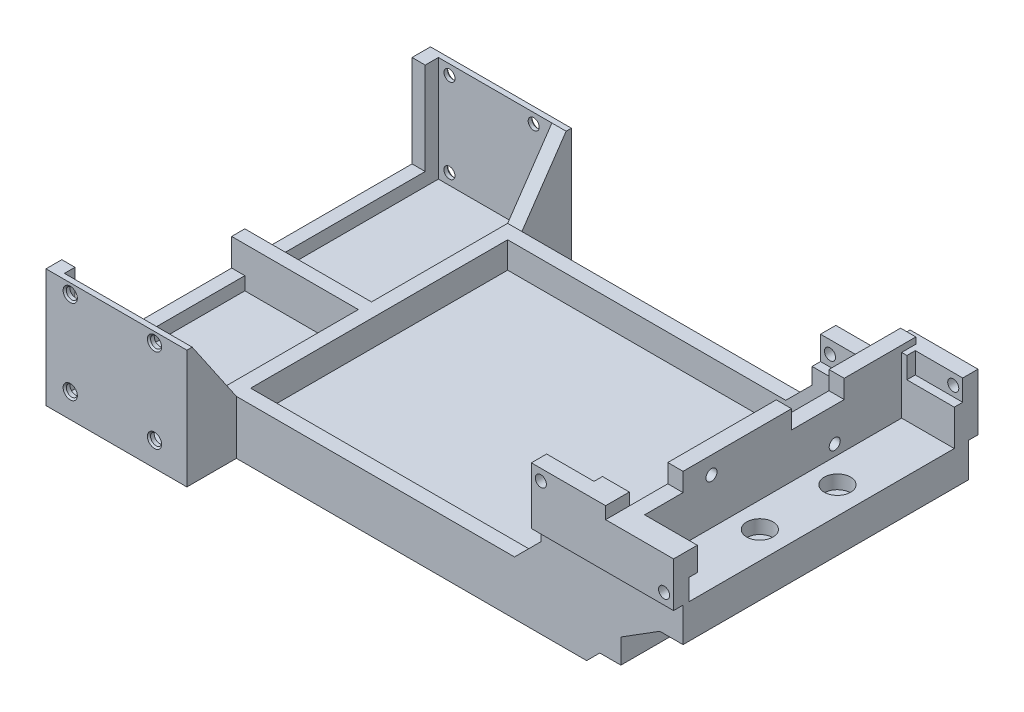
SolidWorks part; units mm, degrees
ref_plane "Front Plane" through (0, 0, 0) normal (0, 0, 1) x (1, 0, 0)
ref_plane "Top Plane" through (0, 0, 0) normal (0, 1, 0) x (1, 0, 0)
ref_plane "Right Plane" through (0, 0, 0) normal (1, 0, 0) x (0, 0, -1)
sketch "Sketch1" plane through (0, 0, 0) normal (0, 1, 0) x (1, 0, 0)
  line L0 (-12.1, 32.5) -> (-12.1, 35.5)
  line L1 (87.8983, -32.4) -> (60.8983, -32.4)
  line L2 (87.8983, -32.4) -> (87.8983, -47)
  line L3 (87.8983, -47) -> (60.8983, -47)
  line L4 (60.8983, -32.4) -> (60.8983, -47)
  line L5 (87.3, 13.5) -> (101.9, 13.5)
  line L6 (87.3, 13.5) -> (87.3, -13.5)
  line L7 (87.3, -13.5) -> (101.9, -13.5)
  line L8 (101.9, 13.5) -> (101.9, -13.5)
  line L9 (60.8983, 32.4) -> (87.8983, 32.4)
  line L10 (60.8983, 32.4) -> (60.8983, 47)
  line L11 (60.8983, 47) -> (87.8983, 47)
  line L12 (87.8983, 32.4) -> (87.8983, 47)
  line L13 (14.3, -24.25) -> (84.3, -24.25)
  line L14 (14.3, -24.25) -> (14.3, 24.25)
  line L15 (14.3, 24.25) -> (84.3, 24.25)
  line L16 (84.3, -24.25) -> (84.3, 24.25)
  line L17 (-12.1, 2.5) -> (10.1, 2.5)
  line L18 (-12.1, 2.5) -> (-12.1, 10.5)
  line L19 (-12.1, 35.5) -> (10.1, 35.5)
  line L20 (10.1, 2.5) -> (10.1, 10.5)
  line L21 (10.1, -35.5) -> (-10.1, -35.5)
  line L22 (10.1, -35.5) -> (10.1, -32.5)
  line L23 (10.1, -2.5) -> (-10.1, -2.5)
  line L24 (-10.1, -35.5) -> (-10.1, -32.5)
  line L25 (-16.1, -32.5) -> (-10.1, -32.5)
  line L26 (-16.1, -32.5) -> (-16.1, -10.5)
  line L27 (-16.1, -10.5) -> (-10.1, -10.5)
  line L28 (11.3, -32.5) -> (11.3, -10.5)
  line L29 (-16.1, 10.5) -> (-12.1, 10.5)
  line L30 (-16.1, 10.5) -> (-16.1, 32.5)
  line L31 (-16.1, 32.5) -> (-12.1, 32.5)
  line L32 (11.3, 10.5) -> (11.3, 32.5)
  line L33 (10.1, 10.5) -> (11.3, 10.5)
  line L34 (10.1, 32.5) -> (10.1, 35.5)
  line L35 (10.1, 32.5) -> (11.3, 32.5)
  line L36 (10.1, -10.5) -> (11.3, -10.5)
  line L37 (10.1, -10.5) -> (10.1, -2.5)
  line L38 (-10.1, -10.5) -> (-10.1, -2.5)
  line L39 (10.1, -32.5) -> (11.3, -32.5)
  arc A0 (90.0992, 6.7139) -> (90.0992, -6.7139) centre (93.8, 0) ccw
  arc A1 (91.0805, -8.0067) -> (96.5195, -8.0067) centre (93.8, -7.366) ccw
  arc A2 (96.5195, 8.0067) -> (91.0805, 8.0067) centre (93.8, 7.366) ccw
  arc A3 (97.5008, -6.7139) -> (97.5008, 6.7139) centre (93.8, 0) ccw
  arc A4 (96.5195, -8.0067) -> (97.5008, -6.7139) centre (98.4662, -8.4654) cw
  arc A5 (90.0992, 6.7139) -> (91.0805, 8.0067) centre (89.1338, 8.4654) ccw
  arc A6 (91.0805, -8.0067) -> (90.0992, -6.7139) centre (89.1338, -8.4654) ccw
  arc A7 (97.5008, 6.7139) -> (96.5195, 8.0067) centre (98.4662, 8.4654) cw
  point P33 (96.585, -7.1425)
  dimension "D1" = 2
  dimension "D2" = 2
  dimension "D3" = 2
  dimension "D36" = 7.6663
  dimension "D37" = 7.366
  dimension "D39" = 2.794
  dimension "D4" = 22.2
  dimension "D5" = 3
  dimension "D6" = 22
  dimension "D7" = 4
  dimension "D8" = 1.2
  dimension "D9" = 3
  dimension "D10" = 70
  dimension "D11" = 48.5
  dimension "D12" = 20.2
  dimension "D13" = 6
  dimension "D14" = 1.2
  dimension "D15" = 3
  dimension "D16" = 22
  dimension "D17" = 8
  dimension "D18" = 3
  dimension "D19" = 11.5
  dimension "D20" = 11.5
  dimension "D21" = 27
  dimension "D22" = 14.6
  dimension "D23" = 27
  dimension "D24" = 14.6
  dimension "D25" = 49.5983
  dimension "D26" = 49.5983
  dimension "D27" = 8
  dimension "D28" = 5
  dimension "D29" = 8.15
  dimension "D30" = 3
  dimension "D31" = 10.75
  dimension "D32" = 9.5
  dimension "D33" = 24.25
  dimension "D34" = 27
  dimension "D35" = 14.6
  dimension "D38" = 7.366
  dimension "D40" = 14.3
  dimension "D41" = 2.5
sketch "Sketch5" plane through (0, 0, 0) normal (0, 1, 0) x (1, 0, 0)
  line L0 (87.15, 27.1) -> (11.45, 27.1)
  line L1 (84.3, 24.25) -> (14.3, 24.25) construction
  line L2 (84.3, 24.25) -> (84.3, -24.25) construction
  line L3 (84.3, -24.25) -> (14.3, -24.25) construction
  line L4 (14.3, 24.25) -> (14.3, -24.25) construction
  line L5 (11.45, 27.1) -> (11.45, -27.1)
  line L6 (87.15, -27.1) -> (11.45, -27.1)
  line L7 (87.15, 27.1) -> (87.15, 3.8718)
  line L8 (87.15, -3.8718) -> (87.15, -27.1)
  line L9 (14.15, 24.4) -> (14.15, -24.4)
  line L10 (87.15, 27.1) -> (87.15, -27.1) construction
  line L11 (84.45, -24.4) -> (14.15, -24.4)
  line L12 (84.45, 24.4) -> (84.45, -24.4)
  line L13 (84.45, 24.4) -> (14.15, 24.4)
  arc A0 (87.15, 3.8718) -> (87.15, -3.8718) centre (93.8, 0) ccw
  dimension "D2" = 15.39
  dimension "D1" = 2.85
  dimension "D3" = 0.15
extrude "Boss-Extrude2" add sketch "Sketch5" along normal blind 5
sketch "Sketch6" plane through (0, 0, 0) normal (0, -1, 0) x (1, 0, 0)
  line L0 (87.15, -3.8718) -> (87.15, -27.1)
  line L1 (11.45, 27.1) -> (87.15, 27.1)
  line L2 (11.45, 27.1) -> (11.45, -27.1)
  line L3 (11.45, -27.1) -> (87.15, -27.1)
  line L4 (87.15, 27.1) -> (87.15, 3.8718)
  arc A0 (87.15, 3.8718) -> (87.15, -3.8718) centre (93.8, 0) ccw
  dimension "D1" = 15.39
extrude "Boss-Extrude4" add sketch "Sketch6" along normal blind 2.7
sketch "Sketch7" plane through (0, 5, 0) normal (0, 1, 0) x (1, 0, 0)
  line L1 (87.15, -27.1) -> (79.15, -27.1)
  line L2 (11.45, -27.1) -> (87.15, -27.1) construction
  line L3 (79.15, -27.1) -> (79.15, -24.4)
  line L4 (14.15, -24.4) -> (84.45, -24.4) construction
  line L5 (79.15, -24.4) -> (84.45, -24.4)
  line L6 (84.45, -24.4) -> (84.45, 24.4)
  line L7 (84.45, 24.4) -> (79.15, 24.4)
  line L8 (84.45, 24.4) -> (14.15, 24.4) construction
  line L9 (79.15, 24.4) -> (79.15, 27.1)
  line L10 (87.15, 27.1) -> (11.45, 27.1) construction
  line L11 (79.15, 27.1) -> (87.15, 27.1)
  line L14 (87.15, 27.1) -> (87.15, 3.8718)
  line L15 (87.15, -3.8718) -> (87.15, -27.1)
  arc A0 (87.15, 3.8718) -> (87.15, -3.8718) centre (93.8, 0) ccw
  dimension "D1" = 15.39
  dimension "D2" = 8
  dimension "D3" = 8
extrude "Boss-Extrude5" add sketch "Sketch7" along normal blind 1.575
sketch "Sketch8" plane through (0, 6.575, 0) normal (0, 1, 0) x (1, 0, 0)
  line L0 (79.15, -27.1) -> (87.15, -27.1) construction
  line L1 (84.45, -27.1) -> (101.95, -27.1)
  line L2 (84.45, -27.1) -> (84.45, 27.1)
  line L3 (84.45, 27.1) -> (101.95, 27.1)
  line L4 (101.95, -27.1) -> (101.95, 27.1)
  line L5 (84.45, -27.1) -> (87.15, -27.1) construction
  dimension "D1" = 54.2
  dimension "D2" = 17.5
  dimension "D3" = 2.7
extrude "Boss-Extrude6" add sketch "Sketch8" along normal blind 6.5
sketch "Sketch9" plane through (0, 0, 27.1) normal (0, 0, 1) x (1, 0, 0)
  line L0 (84.45, 13.075) -> (79.15, 6.575)
  line L1 (79.15, 6.575) -> (84.45, 6.575)
  line L2 (84.45, 6.575) -> (84.45, 13.075)
extrude "Boss-Extrude7" add sketch "Sketch9" against normal through all
sketch "Sketch10" plane through (0, 0, 0) normal (0, 1, 0) x (1, 0, 0)
  line L0 (84.45, 27.1) -> (84.45, -27.1) construction
  line L1 (14.15, 24.4) -> (84.45, 24.4)
  line L2 (14.15, 24.4) -> (14.15, -24.4)
  line L3 (14.15, -24.4) -> (84.45, -24.4)
  line L4 (84.45, 24.4) -> (84.45, -24.4)
  line L5 (14.15, -24.4) -> (84.45, -24.4) construction
extrude "Cut-Extrude1" cut sketch "Sketch10" along normal through all
sketch "Sketch11" plane through (0, 0, 27.1) normal (0, 0, 1) x (1, 0, 0)
  line L0 (94.55, 6.575) -> (87.15, 1.9375)
  line L1 (87.15, 6.575) -> (101.95, 6.575) construction
  line L2 (87.15, 6.575) -> (87.15, -2.7) construction
  line L3 (87.15, 1.9375) -> (87.15, 6.575)
  line L4 (87.15, 6.575) -> (94.55, 6.575)
extrude "Boss-Extrude8" add sketch "Sketch11" against normal blind 5
sketch "Sketch12" plane through (0, 0, -27.1) normal (0, 0, -1) x (-1, 0, 0)
  line L0 (-94.55, 6.575) -> (-87.15, 1.9375)
  line L1 (-101.95, 6.575) -> (-87.15, 6.575) construction
  line L2 (-87.15, 6.575) -> (-87.15, -2.7) construction
  line L3 (-87.15, 1.9375) -> (-87.15, 6.575)
  line L4 (-87.15, 6.575) -> (-94.55, 6.575)
extrude "Boss-Extrude9" add sketch "Sketch12" against normal blind 5
sketch "Sketch13" plane through (0, 13.075, 0) normal (0, 1, 0) x (1, 0, 0)
  line L1 (84.45, 27.1) -> (88.95, 27.1)
  line L2 (84.45, 27.1) -> (84.45, -27.1)
  line L3 (84.45, -27.1) -> (88.95, -27.1)
  line L4 (88.95, 27.1) -> (88.95, -27.1)
  dimension "D1" = 4.5
extrude "Boss-Extrude10" add sketch "Sketch13" along normal blind 12
sketch "Sketch15" plane through (0, 13.075, 0) normal (0, 1, 0) x (1, 0, 0)
  circle A0 centre (93.8, 7.366) radius 1
  circle A1 centre (93.8, -7.366) radius 1
  dimension "D1" = 2
  dimension "D2" = 2
extrude "Cut-Extrude3" cut sketch "Sketch15" against normal through all
sketch "Sketch16" plane through (0, 13.075, 0) normal (0, 1, 0) x (1, 0, 0)
  circle A0 centre (93.8, 7.366) radius 2.5
  circle A1 centre (93.8, -7.366) radius 2.5
  dimension "D1" = 5
extrude "Cut-Extrude4" cut sketch "Sketch16" against normal offset from surface (2.6 mm away) 3.9 up to face at (93.8, 6.575, -8.366)
sketch "Sketch17" plane through (0, 13.075, 0) normal (0, 1, 0) x (1, 0, 0)
  line L0 (88.95, -27.1) -> (101.95, -27.1) construction
  line L1 (101.95, 27.1) -> (98.95, 27.1)
  line L2 (101.95, 27.1) -> (101.95, -27.1)
  line L3 (101.95, -27.1) -> (98.95, -27.1)
  line L4 (98.95, 27.1) -> (98.95, -27.1)
  dimension "D1" = 3
extrude "Cut-Extrude5" cut sketch "Sketch17" against normal through all
sketch "Sketch18" plane through (84.45, 0, 0) normal (-1, 0, 0) x (0, 0, 1)
  line L0 (0, 25.075) -> (-13.5, 25.075) construction
  line L1 (-27.1, 25.075) -> (27.1, 25.075) construction
  line L3 (-13.5, 25.075) -> (-3.5, 25.075)
  line L4 (-13.5, 25.075) -> (-13.5, 21.575)
  line L5 (-13.5, 21.575) -> (-3.5, 21.575)
  line L6 (-3.5, 25.075) -> (-3.5, 21.575)
  dimension "D1" = 13.5
  dimension "D2" = 8.5
  dimension "D3" = 10
extrude "Cut-Extrude6" cut sketch "Sketch18" against normal through all
sketch "Sketch19" plane through (88.95, 0, 0) normal (1, 0, 0) x (0, 0, -1)
  line L0 (-27.1, 25.075) -> (27.1, 25.075) construction
  line L1 (0, 13.075) -> (0, 23.875) construction
  line L3 (-11.7, 18.475) -> (11.7, 18.475) construction
  line L4 (11.7, 18.475) -> (11.7, 15.175) construction
  line L5 (-11.7, 18.475) -> (-11.7, 21.775) construction
  line L6 (27.1, 13.075) -> (-27.1, 13.075) construction
  circle A0 centre (-11.7, 21.775) radius 1.05
  circle A1 centre (11.7, 15.175) radius 1.05
  point P11 (0, 18.475)
  point P15 (0, 18.475)
  dimension "D3" = 2.1
  dimension "D4" = 2.1
  dimension "D1" = 23.4
  dimension "D2" = 2.1
  dimension "D5" = 10.8
extrude "Cut-Extrude7" cut sketch "Sketch19" against normal through all
sketch "Sketch20" plane through (0, 25.075, 0) normal (0, 1, 0) x (1, 0, 0)
  line L0 (88.95, 27.1) -> (84.45, 27.1) construction
  line L1 (84.45, -27.1) -> (86.05, -27.1)
  line L2 (84.45, -27.1) -> (84.45, 27.1)
  line L3 (84.45, 27.1) -> (86.05, 27.1)
  line L4 (86.05, -27.1) -> (86.05, 27.1)
  dimension "D1" = 1.6
extrude "Cut-Extrude8" cut sketch "Sketch20" against normal up to vertex (12 mm away) up to point (84.45, 13.075, -24.4)
sketch "Sketch21" plane through (0, 0, 27.1) normal (0, 0, 1) x (1, 0, 0)
  line L0 (98.95, 13.075) -> (98.95, 15.175) construction
  line L1 (88.95, 13.075) -> (98.95, 13.075)
  line L2 (88.95, 13.075) -> (88.95, 18.075)
  line L3 (88.95, 18.075) -> (98.95, 18.075)
  line L4 (98.95, 13.075) -> (98.95, 18.075)
  line L5 (98.95, 15.175) -> (97.15, 15.175) construction
  line L6 (98.95, 6.575) -> (98.95, 13.075) construction
  circle A0 centre (97.15, 15.175) radius 1.05
  point P8 (98.9208, 15.175)
  dimension "D4" = 2.1
  dimension "D1" = 5
  dimension "D2" = 2.1
  dimension "D3" = 1.8
extrude "Boss-Extrude11" add sketch "Sketch21" against normal blind 2.7 and the other way blind 1.8
sketch "Sketch23" plane through (0, 0, 27.1) normal (0, 0, 1) x (1, 0, 0)
  line L0 (71.95, 23.875) -> (71.95, 21.775) construction
  line L1 (98.95, 13.075) -> (71.95, 13.075)
  line L2 (98.95, 13.075) -> (98.95, 23.875)
  line L3 (98.95, 23.875) -> (71.95, 23.875)
  line L4 (71.95, 13.075) -> (71.95, 23.875)
  line L5 (71.95, 21.775) -> (73.75, 21.775) construction
  circle A0 centre (73.75, 21.775) radius 1.05
  circle A1 centre (97.15, 15.175) radius 1.05
  dimension "D5" = 2.1
  dimension "D6" = 2.1
  dimension "D1" = 10.8
  dimension "D2" = 27
  dimension "D3" = 2.1
  dimension "D4" = 1.8
extrude "Boss-Extrude13" add sketch "Sketch23" along normal blind 1.8 and the other way blind 2.7
sketch "Sketch22" plane through (86.05, 0, 0) normal (-1, 0, 0) x (0, 0, 1)
  line L0 (27.1, 25.075) -> (33.6651, 25.075)
  line L1 (27.1, 25.075) -> (17.1, 25.075)
  line L3 (27.1, 21.575) -> (17.1, 21.575)
  line L4 (17.1, 25.075) -> (17.1, 21.575)
  line L5 (33.6651, 25.075) -> (33.6651, 21.575)
  line L6 (33.6651, 21.575) -> (27.1, 21.575)
  dimension "D2" = 10
  dimension "D3" = 3.5
extrude "Cut-Extrude9" cut sketch "Sketch22" against normal through all
sketch "Sketch24" plane through (0, 0, 27.1) normal (0, 0, 1) x (1, 0, 0)
  line L1 (71.95, 13.075) -> (85.45, 13.075)
  line L2 (71.95, 13.075) -> (71.95, 5)
  line L3 (71.95, 5) -> (85.45, 5)
  line L4 (85.45, 13.075) -> (85.45, 5)
extrude "Boss-Extrude14" add sketch "Sketch24" against normal up to surface (2.7 mm away) up to face at (59.25, 4.9417, 24.4)
sketch "Sketch25" plane through (0, 0, -27.1) normal (0, 0, -1) x (-1, 0, 0)
  line L0 (-98.95, 23.875) -> (-98.95, 21.775) construction
  line L1 (-98.95, 13.075) -> (-71.95, 13.075)
  line L2 (-98.95, 13.075) -> (-98.95, 23.875)
  line L3 (-98.95, 23.875) -> (-86.05, 23.875)
  line L5 (-98.95, 21.775) -> (-97.15, 21.775) construction
  line L6 (-71.95, 13.075) -> (-71.95, 15.175) construction
  line L7 (-71.95, 15.175) -> (-73.75, 15.175) construction
  line L9 (-71.95, 17.575) -> (-80.95, 17.575)
  line L10 (-80.95, 17.575) -> (-86.05, 23.875)
  line L11 (-71.95, 17.575) -> (-71.95, 13.075)
  circle A0 centre (-97.15, 21.775) radius 1.05
  circle A1 centre (-73.75, 15.175) radius 1.05
  point P1 (-73.2063, 14.7578)
  dimension "D3" = 2.1
  dimension "D1" = 2.1
  dimension "D2" = 1.8
  dimension "D4" = 2.1
  dimension "D5" = 1.8
  dimension "D6" = 4.5
  dimension "D7" = 9
  dimension "D8" = 27
extrude "Boss-Extrude15" add sketch "Sketch25" along normal blind 1.8 and the other way blind 2.7
sketch "Sketch26" plane through (0, 0, -24.4) normal (0, 0, 1) x (1, 0, 0)
  line L0 (84.45, 13.075) -> (71.95, 13.075) construction
  line L1 (71.95, 17.575) -> (80.95, 17.575)
  line L2 (71.95, 17.575) -> (71.95, 13.075)
  line L3 (71.95, 13.075) -> (80.95, 13.075)
  line L4 (80.95, 17.575) -> (80.95, 13.075)
extrude "Cut-Extrude10" cut sketch "Sketch26" against normal blind 1.6
sketch "Sketch27" plane through (0, 0, 24.4) normal (0, 0, -1) x (-1, 0, 0)
  line L1 (-71.95, 23.875) -> (-80.95, 23.875)
  line L2 (-71.95, 23.875) -> (-71.95, 19.875)
  line L3 (-71.95, 19.875) -> (-80.95, 19.875)
  line L4 (-80.95, 23.875) -> (-80.95, 19.875)
  dimension "D1" = 4
  dimension "D2" = 9
extrude "Cut-Extrude11" cut sketch "Sketch27" against normal blind 1.6
sketch "Sketch28" plane through (0, 0, -24.4) normal (0, 0, 1) x (1, 0, 0)
  line L1 (98.95, 23.875) -> (89.95, 23.875)
  line L2 (98.95, 23.875) -> (98.95, 19.875)
  line L3 (98.95, 19.875) -> (89.95, 19.875)
  line L4 (89.95, 23.875) -> (89.95, 19.875)
  dimension "D1" = 4
  dimension "D2" = 9
extrude "Cut-Extrude12" cut sketch "Sketch28" against normal blind 1.6
sketch "Sketch29" plane through (0, 0, 24.4) normal (0, 0, -1) x (-1, 0, 0)
  line L1 (-98.95, 13.075) -> (-89.95, 13.075)
  line L2 (-98.95, 13.075) -> (-98.95, 17.075)
  line L3 (-98.95, 17.075) -> (-89.95, 17.075)
  line L4 (-89.95, 13.075) -> (-89.95, 17.075)
  dimension "D1" = 4
  dimension "D2" = 9
extrude "Cut-Extrude13" cut sketch "Sketch29" against normal blind 1.6
sketch "Sketch30" plane through (0, 0, -27.1) normal (0, 0, -1) x (-1, 0, 0)
  line L1 (-71.95, 13.075) -> (-86.6707, 13.075)
  line L2 (-71.95, 13.075) -> (-71.95, 5)
  line L3 (-71.95, 5) -> (-86.6707, 5)
  line L4 (-86.6707, 13.075) -> (-86.6707, 5)
extrude "Boss-Extrude16" add sketch "Sketch30" against normal blind 2.7
sketch "Sketch31" plane through (0, -2.7, 0) normal (0, -1, 0) x (1, 0, 0)
  line L0 (87.15, 27.1) -> (80.65, 27.1) construction
  line L1 (87.15, 27.1) -> (11.45, 27.1) construction
  line L3 (80.65, 27.1) -> (-12.6, 27.1)
  line L4 (80.65, 27.1) -> (80.65, -27.1)
  line L5 (80.65, -27.1) -> (-12.6, -27.1)
  line L6 (-12.6, 27.1) -> (-12.6, -27.1)
  dimension "D1" = 6.5
  dimension "D2" = 24.05
extrude "Boss-Extrude17" add sketch "Sketch31" along normal blind 2.5
sketch "Sketch33" plane through (0, -5.2, 0) normal (0, -1, 0) x (1, 0, 0)
  line L0 (-12.6, 0) -> (0, 0) construction
  line L1 (-12.6, 27.1) -> (-12.6, -27.1) construction
  line L2 (-12.6, -1.25) -> (11.45, -1.25)
  line L3 (-12.6, 1.25) -> (11.45, 1.25)
  line L4 (0, 0) -> (11.45, 0) construction
  line L5 (11.45, 27.1) -> (11.45, -27.1) construction
  line L6 (-12.6, -1.25) -> (0, -1.25) construction
  line L7 (-12.6, 1.25) -> (0, 1.25) construction
  line L8 (-12.6, 1.25) -> (-12.6, -1.25)
  line L9 (11.45, 1.25) -> (11.45, -1.25)
  dimension "D1" = 1.25
  dimension "D2" = 1.25
extrude "Boss-Extrude18" add sketch "Sketch33" against normal up to surface (10.2 mm away) up to face at (42.375, 5, 0)
sketch "Sketch36" plane through (0, -5.2, 0) normal (0, -1, 0) x (1, 0, 0)
  line L1 (-12.6, 27.1) -> (11.45, 27.1)
  line L2 (-12.6, 27.1) -> (-12.6, 36.5)
  line L3 (-12.6, 36.5) -> (11.45, 36.5)
  line L4 (11.45, 27.1) -> (11.45, 36.5)
  point P5 (0, 0)
  point P7 (0, 0)
  point P8 (0, 0)
  point P9 (0, 0)
  dimension "D1" = 9.4
extrude "Boss-Extrude20" add sketch "Sketch36" against normal up to surface (2.5 mm away) up to face at (-0.575, -2.7, 14.175)
sketch "Sketch37" plane through (0, -2.7, 0) normal (0, 1, 0) x (1, 0, 0)
  line L0 (11.45, -27.1) -> (11.45, -36.5) construction
  line L1 (-12.6, -36.5) -> (11.45, -36.5)
  line L2 (-12.6, -36.5) -> (-12.6, -35.5)
  line L3 (-12.6, -35.5) -> (11.45, -35.5)
  line L4 (11.45, -36.5) -> (11.45, -35.5)
  dimension "D1" = 1
extrude "Boss-Extrude21" add sketch "Sketch37" along normal blind 20
sketch "Sketch38" plane through (0, 0, 36.5) normal (0, 0, 1) x (1, 0, 0)
  line L0 (0, 17.3) -> (8, 17.3) construction
  line L1 (-12.6, 17.3) -> (11.45, 17.3) construction
  line L2 (8, 17.3) -> (8, 15.4) construction
  line L3 (8, 15.4) -> (-8, 15.4) construction
  line L4 (8, 15.4) -> (8, -0.6) construction
  line L5 (-8, 15.4) -> (-8, -0.6) construction
  circle A0 centre (8, 15.4) radius 1.05
  circle A1 centre (8, -0.6) radius 1.05
  circle A2 centre (-8, 15.4) radius 1.05
  circle A3 centre (-8, -0.6) radius 1.05
  point P12 (0, 0)
  point P14 (-8.0018, 15.3)
  dimension "D3" = 2.1
  dimension "D1" = 8
  dimension "D2" = 1.9
  dimension "D4" = 16
  dimension "D5" = 16
  dimension "D6" = 16
extrude "Cut-Extrude14" cut sketch "Sketch38" against normal up to next
sketch "Sketch39" plane through (0, -2.7, 0) normal (0, 1, 0) x (1, 0, 0)
  line L0 (11.45, -27.1) -> (71.95, -27.1) construction
  line L1 (11.45, -36.5) -> (14.15, -36.5)
  line L2 (11.45, -36.5) -> (11.45, -27.1)
  line L3 (11.45, -27.1) -> (14.15, -27.1)
  line L4 (14.15, -36.5) -> (14.15, -27.1)
  point P7 (17.2566, -36.5)
  dimension "D1" = 2.7
extrude "Boss-Extrude22" add sketch "Sketch39" along normal up to surface (7.7 mm away) and the other way up to surface (2.5 mm away) up to face at (28.0583, 5, 0) other way up to face at (26.5, -5.2, 12.1667)
sketch "Sketch40" plane through (0, 5, 0) normal (0, 1, 0) x (1, 0, 0)
  line L1 (14.15, -36.5) -> (11.45, -36.5)
  line L2 (14.15, -36.5) -> (14.15, -35.5)
  line L3 (14.15, -35.5) -> (11.45, -35.5)
  line L4 (11.45, -36.5) -> (11.45, -35.5)
extrude "Boss-Extrude23" add sketch "Sketch40" along normal up to surface (12.3 mm away) up to face at (-0.575, 17.3, 36)
sketch "Sketch41" plane through (14.15, 0, 0) normal (1, 0, 0) x (0, 0, -1)
  line L0 (-27.1, 5) -> (-35.5, 17.3)
  line L1 (-35.5, 17.3) -> (-35.5, 5)
  line L2 (-35.5, 5) -> (-27.1, 5)
extrude "Boss-Extrude24" add sketch "Sketch41" against normal up to surface (2.7 mm away) up to face at (11.45, 1.15, -14.175)
sketch "Sketch42" plane through (0, -2.7, 0) normal (0, 1, 0) x (1, 0, 0)
  line L1 (-12.6, -35.5) -> (-10.1, -35.5)
  line L2 (-12.6, -35.5) -> (-12.6, -33.5)
  line L3 (-12.6, -33.5) -> (-10.1, -33.5)
  line L4 (-10.1, -35.5) -> (-10.1, -33.5)
  dimension "D1" = 2.5
  dimension "D2" = 2
extrude "Boss-Extrude25" add sketch "Sketch42" along normal up to surface (20 mm away) up to face at (2.91, 17.3, 35.9)
sketch "Sketch43" plane through (0, -2.7, 0) normal (0, 1, 0) x (1, 0, 0)
  line L1 (-12.6, 27.1) -> (11.45, 27.1)
  line L2 (-12.6, 27.1) -> (-12.6, 36.5)
  line L3 (-12.6, 36.5) -> (11.45, 36.5)
  line L4 (11.45, 27.1) -> (11.45, 36.5)
  point P5 (0, 0)
  point P6 (0, 0)
  point P7 (0, 0)
  dimension "D1" = 9.4
extrude "Boss-Extrude26" add sketch "Sketch43" against normal up to surface (2.5 mm away) up to face at (27.4, -5.2, 12.1667)
sketch "Sketch44" plane through (0, -2.7, 0) normal (0, 1, 0) x (1, 0, 0)
  line L0 (11.45, 27.1) -> (11.45, 36.5) construction
  line L1 (-12.6, 36.5) -> (11.45, 36.5)
  line L2 (-12.6, 36.5) -> (-12.6, 35.5)
  line L3 (-12.6, 35.5) -> (11.45, 35.5)
  line L4 (11.45, 36.5) -> (11.45, 35.5)
  dimension "D1" = 1
extrude "Boss-Extrude27" add sketch "Sketch44" along normal up to surface (20 mm away) up to face at (-0.8071, 17.3, 35.2143)
sketch "Sketch45" plane through (0, -2.7, 0) normal (0, 1, 0) x (1, 0, 0)
  line L0 (71.95, 27.1) -> (11.45, 27.1) construction
  line L1 (11.45, 36.5) -> (14.15, 36.5)
  line L2 (11.45, 36.5) -> (11.45, 27.1)
  line L3 (11.45, 27.1) -> (14.15, 27.1)
  line L4 (14.15, 36.5) -> (14.15, 27.1)
  dimension "D1" = 2.7
extrude "Boss-Extrude30" add sketch "Sketch45" along normal up to surface (7.7 mm away) and the other way up to surface (2.5 mm away) up to face at (26.9885, 5, 2.0846) other way up to face at (23.4125, -5.2, 0)
sketch "Sketch46" plane through (14.15, 0, 0) normal (1, 0, 0) x (0, 0, -1)
  line L0 (27.1, 5) -> (35.5, 17.3)
  line L1 (35.5, 17.3) -> (36.5, 17.3)
  line L2 (36.5, 17.3) -> (36.5, 5)
  line L3 (36.5, 5) -> (27.1, 5)
extrude "Boss-Extrude31" add sketch "Sketch46" against normal up to surface (2.7 mm away) up to face at (11.45, 11.15, -36)
sketch "Sketch47" plane through (0, -2.7, 0) normal (0, 1, 0) x (1, 0, 0)
  line L1 (-12.6, 35.5) -> (-10.1, 35.5)
  line L2 (-12.6, 35.5) -> (-12.6, 33)
  line L3 (-12.6, 33) -> (-10.1, 33)
  line L4 (-10.1, 35.5) -> (-10.1, 33)
  dimension "D1" = 2.5
  dimension "D2" = 2.5
extrude "Boss-Extrude32" add sketch "Sketch47" along normal up to surface (20 mm away) up to face at (2.91, 17.3, -35.9)
sketch "Sketch48" plane through (0, 0, -36.5) normal (0, 0, -1) x (-1, 0, 0)
  line L0 (0, 0) -> (0, 17.3) construction
  line L1 (12.6, 17.3) -> (-14.15, 17.3) construction
  line L2 (0, 17.3) -> (8, 17.3) construction
  line L3 (8, 17.3) -> (8, 15.4) construction
  line L4 (8, 15.4) -> (-8, 15.4) construction
  line L5 (-8, 15.4) -> (-8, -0.6) construction
  line L6 (8, 15.4) -> (8, -0.6) construction
  circle A0 centre (8, 15.4) radius 1.05
  circle A1 centre (-8, 15.4) radius 1.05
  circle A2 centre (-8, -0.6) radius 1.05
  circle A3 centre (8, -0.6) radius 1.05
  dimension "D3" = 2.1
  dimension "D1" = 8
  dimension "D2" = 1.9
  dimension "D4" = 16
  dimension "D5" = 16
  dimension "D6" = 16
extrude "Cut-Extrude15" cut sketch "Sketch48" against normal up to surface (1 mm away) up to face at (0.675, 7.3, -35.5)
sketch "Sketch49" plane through (0, -2.7, 0) normal (0, 1, 0) x (1, 0, 0)
  line L1 (-10.1, 33) -> (-12.6, 33)
  line L2 (-10.1, 33) -> (-10.1, -33.5)
  line L3 (-10.1, -33.5) -> (-12.6, -33.5)
  line L4 (-12.6, 33) -> (-12.6, -33.5)
extrude "Boss-Extrude33" add sketch "Sketch49" along normal blind 2.5
chamfer "Chamfer1" distance 0.3 angle 45 8 edges at (-9.05, 15.4, -36.5) (6.95, -0.6, -36.5) (-9.05, -0.6, -36.5) (6.95, 15.4, -36.5) (-6.95, -0.6, 36.5) (9.05, -0.6, 36.5) (9.05, 15.4, 36.5) (-6.95, 15.4, 36.5)
chamfer "Chamfer2" distance 2.5 angle 45 1 edges at (80.65, -2.7, 0)
chamfer "Chamfer3" distance 5 angle 45 2 edges at (71.95, 5, -25.75) (71.95, 5, 25.75)
